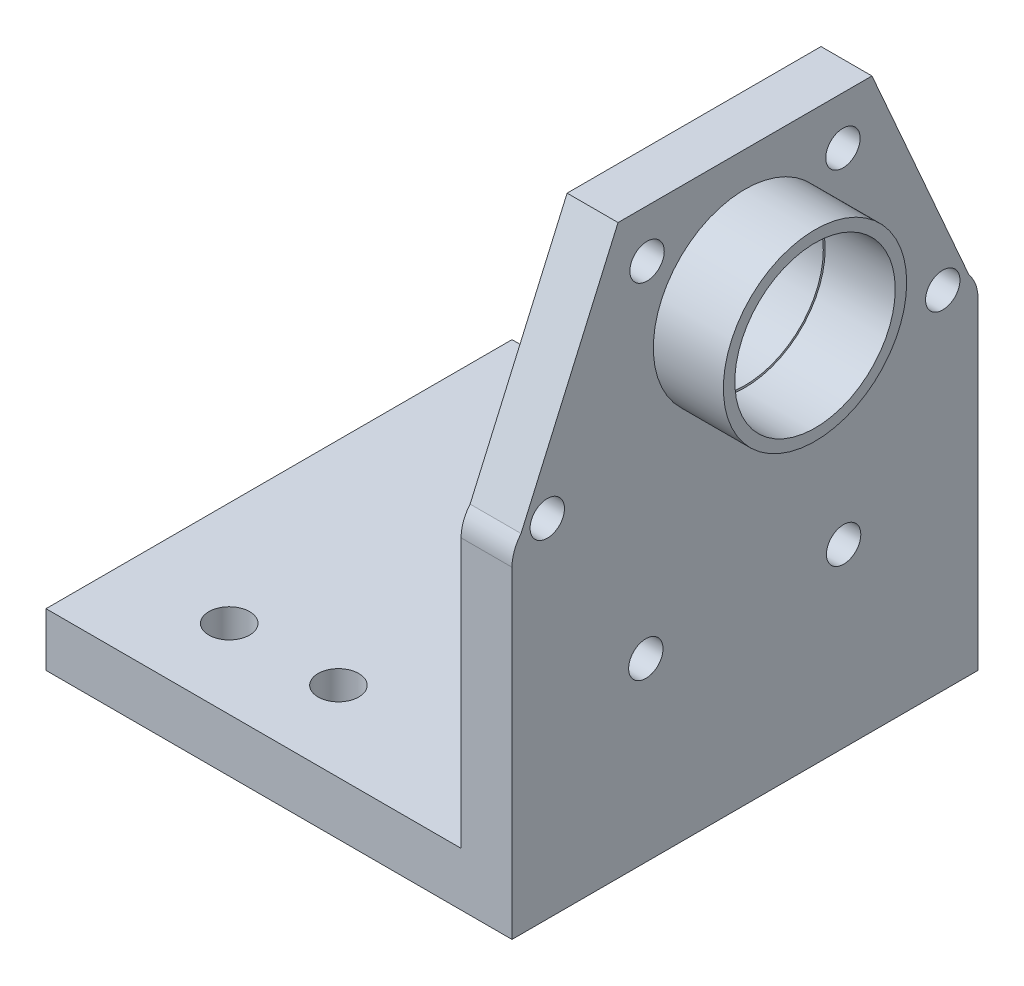
SolidWorks part; units mm, degrees
ref_plane "前视基准面" through (0, 0, 0) normal (0, 0, 1) x (1, 0, 0)
ref_plane "上视基准面" through (0, 0, 0) normal (0, 1, 0) x (1, 0, 0)
ref_plane "右视基准面" through (0, 0, 0) normal (1, 0, 0) x (0, 0, -1)
sketch "草图1" plane through (0, 0, 0) normal (0, 1, 0) x (1, 0, 0)
  line L1 (18.3, -18.3) -> (-18.3, -18.3)
  line L2 (18.3, -18.3) -> (18.3, 18.3)
  line L3 (18.3, 18.3) -> (-18.3, 18.3)
  line L4 (-18.3, -18.3) -> (-18.3, 18.3)
  line L5 (18.3, -18.3) -> (-18.3, 18.3) construction
  line L6 (18.3, 18.3) -> (-18.3, -18.3) construction
  point P0 (0, 0)
  dimension "D1" = 36.6
  dimension "D2" = 36.6
extrude "凸台-拉伸1" add sketch "草图1" along normal blind 40.6 and the other way blind 4
ref_plane "基准面1" through (0, 40.6, 0) normal (0, 1, 0) x (1, 0, 0)
sketch "草图2" plane through (0, 40.6, 0) normal (0, 1, 0) x (1, 0, 0)
  line L0 (-18.3, -18.3) -> (18.3, -18.3) construction
  line L1 (-18.3, 18.3) -> (14.3, 18.3)
  line L2 (-18.3, 18.3) -> (-18.3, -18.3)
  line L3 (-18.3, -18.3) -> (14.3, -18.3)
  line L4 (14.3, 18.3) -> (14.3, -18.3)
  dimension "D1" = 32.6
extrude "切除-拉伸1" cut sketch "草图2" against normal blind 40.4
ref_plane "基准面2" through (18.3, 0, 0) normal (1, 0, 0) x (0, 0, -1)
sketch "草图3" plane through (18.3, 0, 0) normal (1, 0, 0) x (0, 0, -1)
  line L0 (2.2, 40.6) -> (-2.2, 40.6) construction
  line L1 (-18.3, 40.6) -> (18.3, 40.6)
  line L2 (-18.3, 40.6) -> (-18.3, 4)
  line L3 (-18.3, 4) -> (18.3, 4)
  line L4 (18.3, 40.6) -> (18.3, 4)
  line L5 (-18.3, 40.6) -> (-18.3, -4) construction
  line L6 (18.3, 40.6) -> (18.3, -4) construction
  line L7 (0, 40.6) -> (0, 36.8329) construction
  line L8 (0, 36.8329) -> (0, 30.6829) construction
  line L9 (7.692, 36.8329) -> (-7.692, 36.8329)
  line L10 (-7.692, 36.8329) -> (-15.53, 23.257) construction
  line L11 (7.692, 36.8329) -> (15.53, 23.257) construction
  line L12 (-15.53, 23.257) -> (-7.79, 9.851) construction
  line L13 (-7.79, 9.851) -> (7.7452, 9.851) construction
  line L14 (7.7452, 9.851) -> (15.53, 23.257) construction
  circle A0 centre (0, 30.6829) radius 6.15
  circle A1 centre (-7.692, 36.8329) radius 1.35
  circle A2 centre (7.692, 36.8329) radius 1.35
  circle A3 centre (-15.53, 23.257) radius 1.35
  circle A4 centre (15.53, 23.257) radius 1.35
  circle A5 centre (7.7452, 9.851) radius 1.35
  circle A6 centre (-7.79, 9.851) radius 1.35
  point P10 (0, 40.6)
  point P20 (0, 36.8329)
  dimension "D2" = 120
  dimension "D4" = 12.3
  dimension "D1" = 36.6
  dimension "D3" = 120
extrude "切除-拉伸5" cut sketch "草图3" against normal blind 36.6 contours A0 | A1 | A3 | A2 | A4 | A5 | A6 region at (18.3, 30.6829, 0) region at (18.3, 36.8329, 9.0038) region at (18.3, 38.1447, -7.692) region at (18.3, 23.257, 15.53) region at (18.3, 23.257, -15.53) region at (18.3, 9.851, -7.7452) region at (18.3, 9.851, 7.79)
fillet "圆角2" radius 2 2 edges at (16.3, 40.6, 18.3) (16.3, 40.6, -18.3)
ref_plane "基准面3" through (0, -4, 0) normal (0, -1, 0) x (-1, 0, 0)
sketch "草图7" plane through (0, -4, 0) normal (0, -1, 0) x (-1, 0, 0)
  line L0 (-18.0079, 0) -> (18.3, 0) construction
  line L1 (18.3, 18.3) -> (18.3, -18.3) construction
  circle A0 centre (1.6069, 12.025) radius 1.6
  circle A1 centre (10.1066, 12.1035) radius 1.6
  circle A2 centre (10.1066, -12.1035) radius 1.6
  circle A3 centre (1.6069, -12.025) radius 1.6
  dimension "D1" = 8.5
  dimension "D2" = 24.05
extrude "切除-拉伸6" cut sketch "草图7" against normal blind 10
sketch "草图12" plane through (18.3, 0, 0) normal (1, 0, 0) x (0, 0, -1)
  line L0 (-9.042, 36.8329) -> (-18.3, 36.8329) construction
  line L1 (-18.3, 38.6) -> (-18.3, -4) construction
  line L2 (-16.88, 23.257) -> (-18.3, 23.257) construction
  line L3 (-17.59, 23.257) -> (-11.6264, 36.8329)
  line L4 (-11.6264, 36.8329) -> (-9.9716, 40.6)
  line L5 (2.2, 40.6) -> (-2.2, 40.6) construction
  line L6 (-17.59, 23.257) -> (-18.3, 23.257)
  line L7 (-18.3, 23.257) -> (-18.3, 40.6)
  line L8 (-18.3, 40.6) -> (-9.9716, 40.6)
  line L9 (0, 40.6) -> (0, 22.4035) construction
  line L10 (18.3, 23.257) -> (18.3, 40.6)
  line L11 (17.59, 23.257) -> (18.3, 23.257)
  line L12 (17.59, 23.257) -> (11.6264, 36.8329)
  line L13 (11.6264, 36.8329) -> (9.9716, 40.6)
  line L14 (18.3, 40.6) -> (9.9716, 40.6)
  circle A0 centre (-7.692, 36.8329) radius 1.35 construction
  circle A1 centre (-15.53, 23.257) radius 1.35 construction
  point P12 (-17.59, 23.257)
  point P13 (-13.671, 36.8329)
extrude "切除-拉伸8" cut sketch "草图12" against normal blind 10
fillet "圆角5" radius 3 1 edges at (16.3, 23.257, 18.3)
fillet "圆角6" radius 3 1 edges at (16.3, 23.257, -18.3)
sketch "草图17" plane through (18.3, 0, 0) normal (1, 0, 0) x (0, 0, -1)
  circle A0 centre (0, 30.6829) radius 7.2
extrude "凸台-拉伸2" add sketch "草图17" along normal blind 5.5
sketch "草图18" plane through (23.8, 0, 0) normal (1, 0, 0) x (0, 0, -1)
  line L0 (0, 37.8829) -> (0, 23.4829) construction
  circle A0 centre (0, 30.6829) radius 7.2 construction
  circle A1 centre (0, 30.6829) radius 7.2 construction
  circle A2 centre (0, 30.6829) radius 6.3
extrude "切除-拉伸9" cut sketch "草图18" against normal blind 5.5
